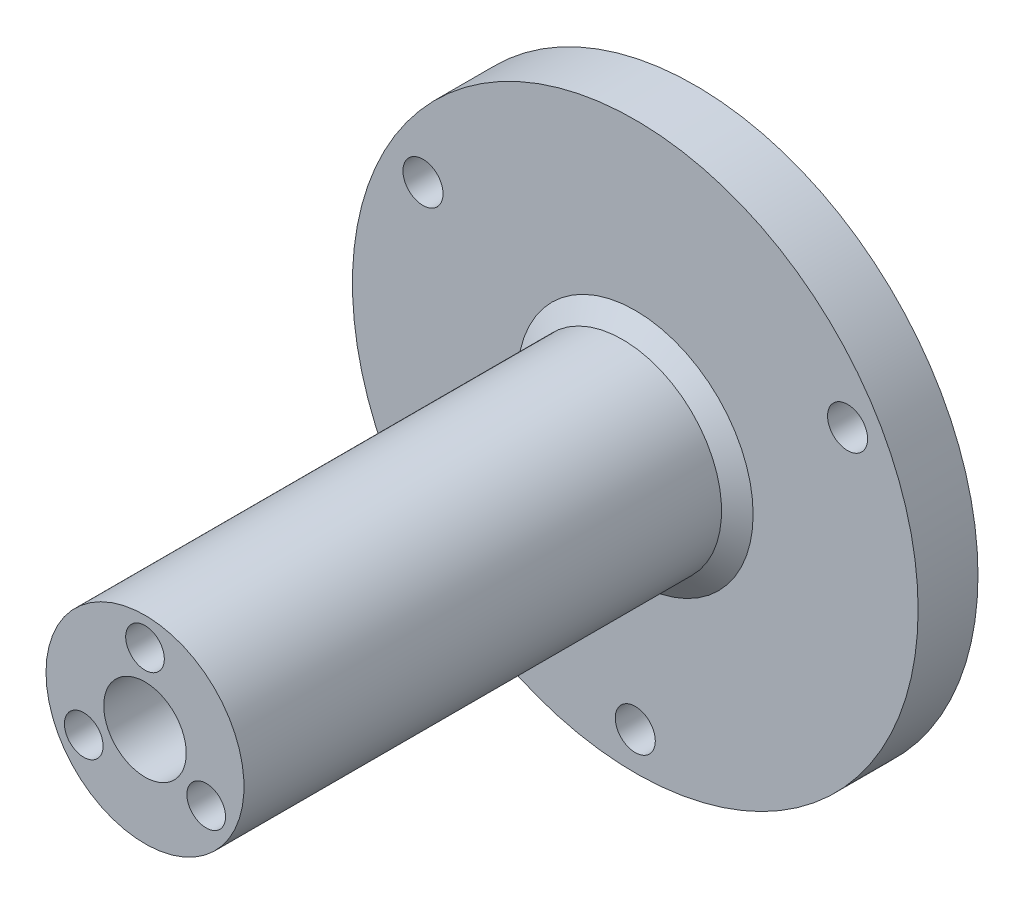
SolidWorks part; units mm, degrees
ref_plane "Plan de face" through (0, 0, 0) normal (0, 0, 1) x (1, 0, 0)
ref_plane "Plan de dessus" through (0, 0, 0) normal (0, 1, 0) x (1, 0, 0)
ref_plane "Plan de droite" through (0, 0, 0) normal (1, 0, 0) x (0, 0, -1)
sketch "Esquisse2" plane through (0, 0, 0) normal (0, 0, 1) x (1, 0, 0)
  circle A0 centre (0, 0) radius 7.5
  circle A1 centre (0, 0) radius 4
  dimension "D1" = 15
  dimension "D2" = 8
sketch "Esquisse1" plane through (0, 0, 0) normal (0, 0, 1) x (1, 0, 0)
  line L0 (-17.5, 10.1036) -> (0, -20.2073) construction
  line L1 (0, -20.2073) -> (17.5, 10.1036) construction
  line L2 (17.5, 10.1036) -> (-17.5, 10.1036) construction
  line L3 (16.0524, 9.2678) -> (-8.4583, -4.8834) construction
  line L4 (0.0575, -0.0332) -> (-30.6383, 17.689) construction
  circle A0 centre (-17.5, 10.1036) radius 1.625
  circle A1 centre (0, -20.2073) radius 1.625
  circle A2 centre (17.5, 10.1036) radius 1.625
  dimension "D2" = 3.25
  dimension "D1" = 35
sketch "Esquisse3" plane through (0, 0, 0) normal (0, 0, 1) x (1, 0, 0)
  line L5 (-22.5167, 13) -> (22.5167, 13) construction
  line L6 (22.5167, 13) -> (0, -26) construction
  line L7 (0, -26) -> (-22.5167, 13) construction
  circle A0 centre (-22.5167, 13) radius 2.125
  circle A1 centre (22.5167, 13) radius 2.125
  circle A2 centre (0, -26) radius 2.125
  circle A7 centre (0, 0) radius 26
  circle A8 centre (0, 0) radius 30
  circle A10 centre (0, 0) radius 7.675
  dimension "D2" = 15.35
  dimension "D1" = 52
  dimension "D3" = 60
  dimension "D4" = 4.25
extrude "Boss.-Extru.1" add sketch "Esquisse3" along normal blind 6.35 contours A8 A7 A1 A2 A0 | A1 A7 A0 A2 A10 region at (-20.0113, 14.379, 0) region at (-29.1515, 0, 0)
sketch "Esquisse4" plane through (0, 0, 6.35) normal (0, 0, 1) x (1, 0, 0)
  circle A2 centre (0, 0) radius 7.675
  circle A3 centre (0, 0) radius 10.5
  circle A4 centre (0, 0) radius 7.675 construction
  dimension "D1" = 21
extrude "Boss.-Extru.2" add sketch "Esquisse4" along normal blind 45
sketch "Sketch1" plane through (0, 0, 51.35) normal (0, 0, 1) x (1, 0, 0)
  circle A0 centre (0, 0) radius 10.5
  circle A1 centre (0, 0) radius 4.375
  circle A2 centre (0, 0) radius 10.5 construction
  dimension "D1" = 8.75
extrude "Boss-Extrude1" add sketch "Sketch1" along normal blind 7
sketch "Sketch2" plane through (0, 0, 58.35) normal (0, 0, 1) x (1, 0, 0)
  line L0 (-6.4952, -3.75) -> (0, 7.5) construction
  line L1 (0, 7.5) -> (6.4952, -3.75) construction
  line L2 (-3.2476, 1.875) -> (6.4952, -3.75) construction
  line L3 (-6.4952, -3.75) -> (3.2476, 1.875) construction
  line L4 (-6.4952, -3.75) -> (6.4952, -3.75) construction
  circle A0 centre (0, 7.5) radius 2.05
  circle A1 centre (-6.4952, -3.75) radius 2.05
  circle A2 centre (6.4952, -3.75) radius 2.05
  circle A3 centre (0, 0) radius 7.5
  point P7 (0, 0)
  dimension "D1" = 4.1
  dimension "D2" = 15
extrude "Cut-Extrude1" cut sketch "Sketch2" against normal blind 6 contours A3 A0 | A0 A3 | A3 A1 | A1 A3 | A3 A2 | A2 A3 region at (0, 8.3176, 58.35) region at (0, 6.5815, 58.35) region at (-7.2033, -4.1588, 58.35) region at (-5.6997, -3.2907, 58.35) region at (5.6997, -3.2907, 58.35) region at (7.2033, -4.1588, 58.35)
chamfer "Chamfer2" distance 4 angle 55 1 edges at (7.675, 0, 51.35) first distance on face at (4.375, 0, 51.35)
chamfer "Chamfer3" distance 2 angle 34 1 edges at (10.5, 0, 6.35) first distance on face at (30, 0, 6.35)
